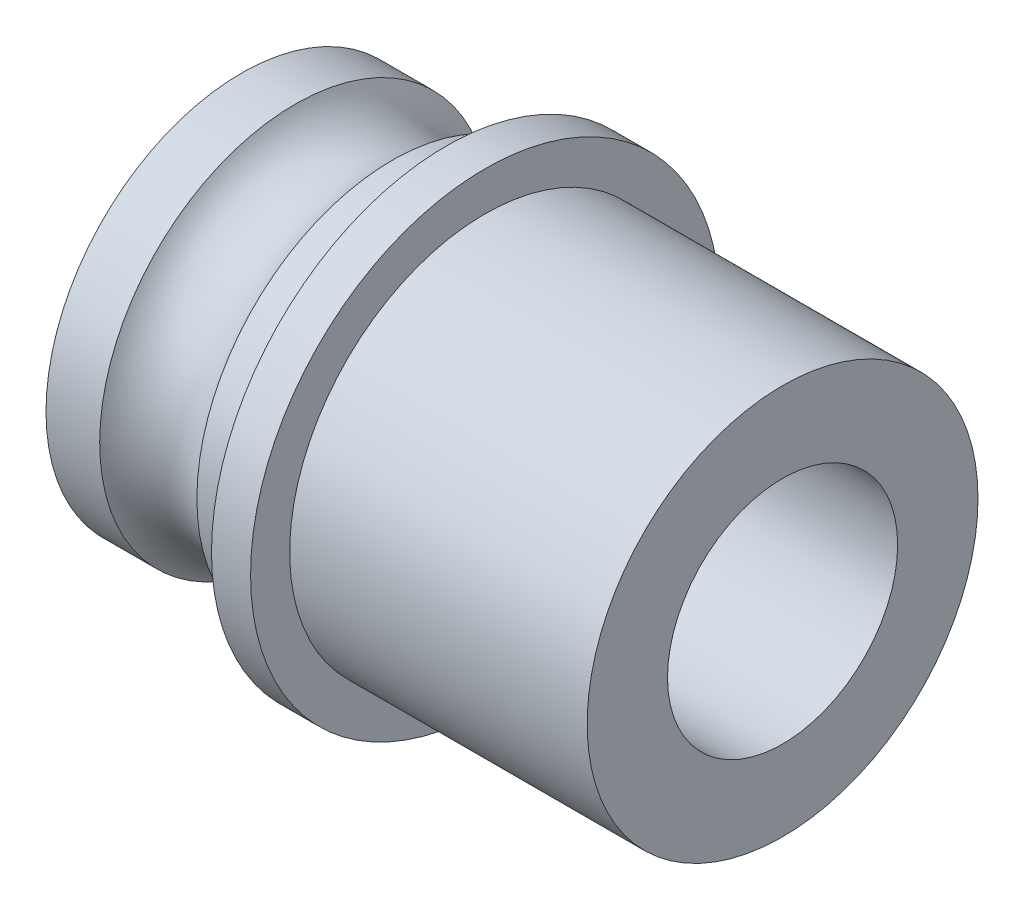
SolidWorks part; units mm, degrees
ref_plane "Front Plane" through (0, 0, 0) normal (0, 0, 1) x (1, 0, 0)
ref_plane "Top Plane" through (0, 0, 0) normal (0, 1, 0) x (1, 0, 0)
ref_plane "Right Plane" through (0, 0, 0) normal (1, 0, 0) x (0, 0, -1)
sketch "Sketch1" plane through (0, 0, 0) normal (0, 0, 1) x (1, 0, 0)
  line L0 (0, 0) -> (4, 0)
  line L1 (0, 0) -> (-4, 0)
  line L2 (-4, 0) -> (-4, 3.142)
  line L3 (4, 0) -> (4, 3.142)
  line L4 (-4, 3.142) -> (-1.9, 3.142)
  line L5 (4, 3.142) -> (1.9, 3.142)
  line L6 (-1.9, 3.142) -> (1.9, 3.142) construction
  line L7 (-4, 3.142) -> (-4, -4.5) construction
  line L8 (-4, -4.5) -> (4, -4.5) construction
  arc A0 (-1.9, 3.142) -> (1.9, 3.142) centre (0, 4.2511) ccw
  dimension "D6" = 2.2
  dimension "D1" = 4
  dimension "D2" = 4
  dimension "D3" = 3.142
  dimension "D4" = 2.1
  dimension "D5" = 7.642
revolve "Revolve1" add sketch "Sketch1" angle 360 about L8
scale "Scale1" bodies to scale 101 scale about centroid uniform scaling yes scale factor 6
sketch "Sketch4" plane through (24, 0, 0) normal (1, 0, 0) x (0, 0, -1)
  circle A0 centre (0, -4.5) radius 45.852
extrude "Boss-Extrude1" add sketch "Sketch4" along normal blind 12.7
sketch "Sketch5" plane through (24, 0, 0) normal (-1, 0, 0) x (0, 0, 1)
  circle A0 centre (0, -4.5) radius 27
extrude "Cut-Extrude1" cut sketch "Sketch5" against normal through all
scale "Scale2" bodies to scale 104 scale about centroid uniform scaling yes scale factor 3.323882
sketch "Sketch7" plane through (105.4144, 0, 0) normal (1, 0, 0) x (0, 0, -1)
  circle A0 centre (0, -4.5) radius 89.7448 construction
  circle A1 centre (0, -4.5) radius 152.4066 construction
  circle A2 centre (0, -4.5) radius 89.7448
  circle A3 centre (0, -4.5) radius 152.4066
extrude "Boss-Extrude2" add sketch "Sketch7" along normal blind 33.99
scale "Scale3" bodies to scale 106 scale about centroid uniform scaling yes scale factor 0.416653
sketch "Sketch8" plane through (72.9418, 0, 0) normal (1, 0, 0) x (0, 0, -1)
  circle A0 centre (0, -4.5) radius 63.5007 construction
  circle A1 centre (0, -4.5) radius 63.5007
  circle A2 centre (0, -4.5) radius 76.2007
  dimension "D1" = 12.7
extrude "Boss-Extrude3" add sketch "Sketch8" along normal blind 12.7 from offset 31.75 contours A2 offset against normal yes
sketch "Sketch9" plane through (72.9418, 0, 0) normal (1, 0, 0) x (0, 0, -1)
  circle A0 centre (0, -4.5) radius 63.5007 construction
  circle A1 centre (0, -4.5) radius 63.5007
  circle A2 centre (0, -4.5) radius 37.3924 construction
  circle A3 centre (0, -4.5) radius 37.3924
extrude "Boss-Extrude4" add sketch "Sketch9" along normal blind 19.05
sketch "Sketch10" plane through (53.8918, 0, 0) normal (1, 0, 0) x (0, 0, -1)
  circle A0 centre (0, -4.5) radius 37.3924 construction
  circle A1 centre (0, -4.5) radius 37.3924
extrude "Cut-Extrude2" cut sketch "Sketch10" against normal through all
scale "Scale4" bodies to scale 110 scale about centroid uniform scaling yes scale factor 0.705392
sketch "Sketch11" plane through (75.6141, 0, 0) normal (1, 0, 0) x (0, 0, -1)
  circle A0 centre (0, -4.5) radius 44.7929 construction
  circle A1 centre (0, -4.5) radius 26.3763 construction
  circle A2 centre (0, -4.5) radius 44.7929
  circle A3 centre (0, -4.5) radius 26.3763
extrude "Boss-Extrude5" add sketch "Sketch11" along normal blind 41.32
scale "Scale5" bodies to scale 112 scale about centroid uniform scaling yes scale factor 0.666667
